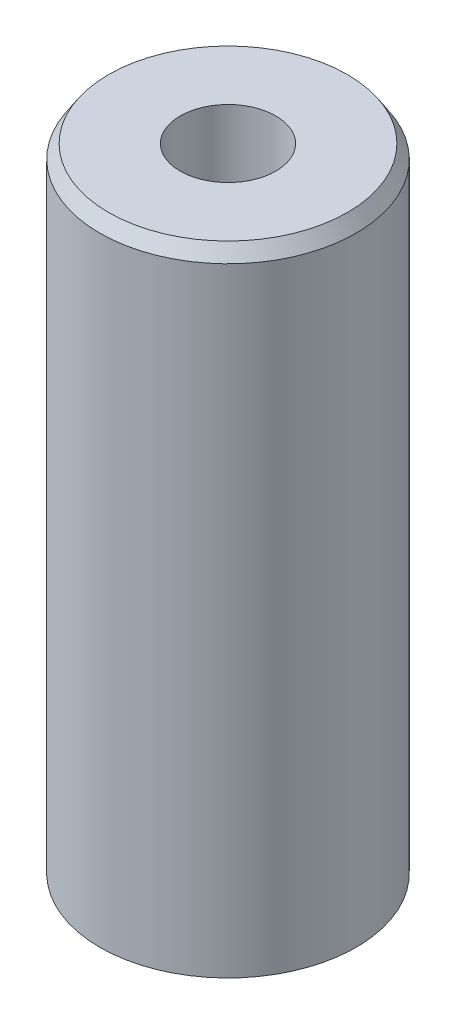
SolidWorks part; units mm, degrees
ref_plane "Front Plane" through (0, 0, 0) normal (0, 0, 1) x (1, 0, 0)
ref_plane "Top Plane" through (0, 0, 0) normal (0, 1, 0) x (1, 0, 0)
ref_plane "Right Plane" through (0, 0, 0) normal (1, 0, 0) x (0, 0, -1)
sketch "Sketch1" plane through (0, 0, 0) normal (0, 1, 0) x (1, 0, 0)
  circle A0 centre (0, 0) radius 10
  dimension "SHAFT_OD" = 20
extrude "Boss-Extrude1" add sketch "Sketch1" along normal blind 49.982
sketch "Sketch2" plane through (0, 0, 0) normal (0, 1, 0) x (1, 0, 0)
  circle A0 centre (0, 0) radius 3.731
  dimension "BORE_D" = 7.462
extrude "Cut-Extrude1" cut sketch "Sketch2" along normal through all
chamfer "Chamfer1" distance 1.0549 angle 32.912 2 edges at (0, 49.982, 10) (0, 0, 10) first distance on face at (0, 49.982, 10) first distance on face at (0, 0, 3.731)
